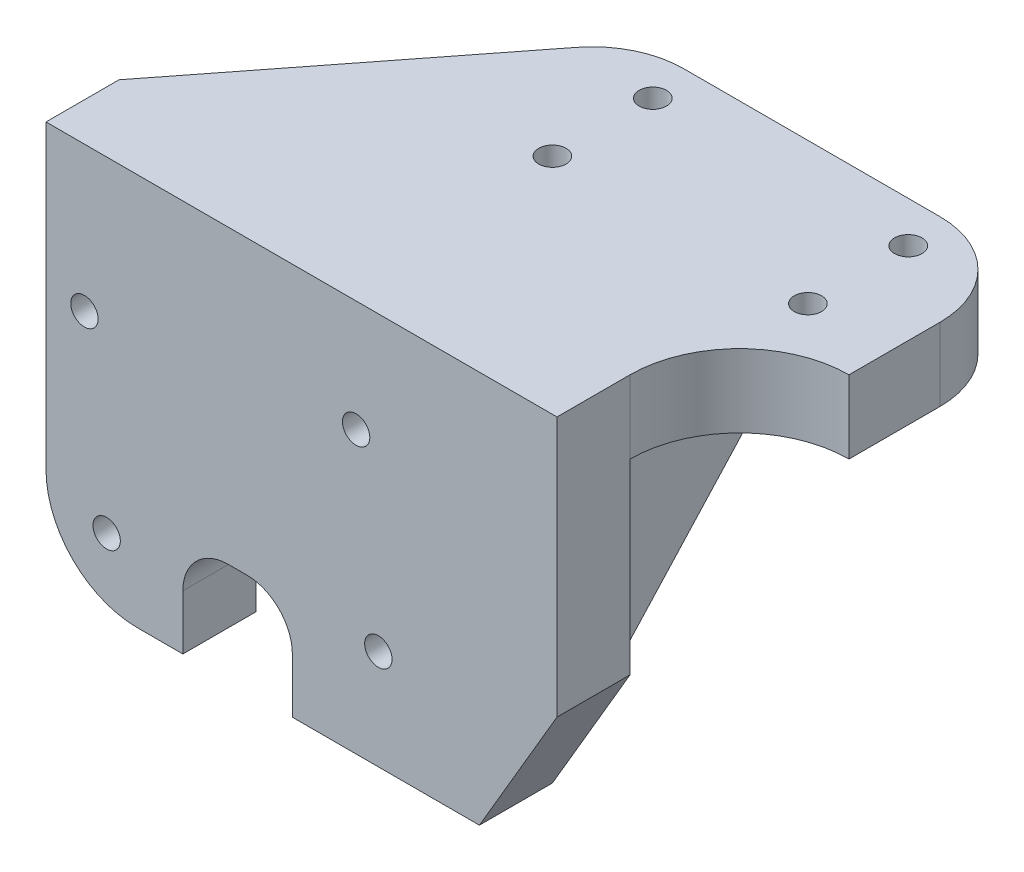
SolidWorks part; units mm, degrees
material "ABS"
ref_plane "前视基准面" through (0, 0, 0) normal (0, 0, 1) x (1, 0, 0)
ref_plane "上视基准面" through (0, 0, 0) normal (0, 1, 0) x (1, 0, 0)
ref_plane "右视基准面" through (0, 0, 0) normal (1, 0, 0) x (0, 0, -1)
sketch "草图1" plane through (0, 0, 0) normal (0, 1, 0) x (1, 0, 0)
  line L1 (-45, -20) -> (45, -20)
  line L2 (-45, -20) -> (-45, 20)
  line L3 (-45, 20) -> (45, 20)
  line L4 (45, -20) -> (45, 20)
  line L5 (-45, -20) -> (45, 20) construction
  line L6 (-45, 20) -> (45, -20) construction
  point P0 (0, 0)
  dimension "D1" = 40
  dimension "D2" = 90
extrude "凸台-拉伸1" add sketch "草图1" along normal blind 8
sketch "草图2" plane through (0, 0, 0) normal (0, -1, 0) x (1, 0, 0)
  line L0 (0, 20) -> (0, -20) construction
  line L1 (-45, 20) -> (45, 20) construction
  line L2 (45, -20) -> (-45, -20) construction
  line L4 (-14, -15.5) -> (14, -15.5) construction
  line L5 (-14, -15.5) -> (-14, -4.5) construction
  line L6 (-14, -4.5) -> (14, -4.5) construction
  line L7 (14, -15.5) -> (14, -4.5) construction
  line L8 (-14, -15.5) -> (14, -4.5) construction
  line L9 (-14, -4.5) -> (14, -15.5) construction
  circle A0 centre (-14, -4.5) radius 1.5
  circle A1 centre (-14, -15.5) radius 1.5
  circle A2 centre (14, -15.5) radius 1.5
  circle A3 centre (14, -4.5) radius 1.5
  point P6 (0, -10)
  dimension "D1" = 3
  dimension "D2" = 3
  dimension "D3" = 11
  dimension "D4" = 10
  dimension "D5" = 28
extrude "切除-拉伸1" cut sketch "草图2" against normal through all
sketch "草图3" plane through (0, 0, 0) normal (0, -1, 0) x (1, 0, 0)
  line L0 (45, 20) -> (45, -20) construction
  line L1 (-45, 20) -> (45, 20)
  line L2 (-45, 20) -> (-45, 12)
  line L3 (-45, 12) -> (45, 12)
  line L4 (45, 20) -> (45, 12)
  dimension "D1" = 8
extrude "凸台-拉伸2" add sketch "草图3" along normal blind 35
sketch "草图6" plane through (0, 0, 0) normal (0, -1, 0) x (1, 0, 0)
  line L0 (-45, 12) -> (-20, -20)
  line L1 (45, -20) -> (-45, -20) construction
  line L2 (-20, -20) -> (-45, -20)
  line L3 (-45, -20) -> (-45, 12)
  dimension "D1" = 25
extrude "切除-拉伸3" cut sketch "草图6" against normal through all
sketch "草图7" plane through (0, 8, 0) normal (0, 1, 0) x (1, 0, 0)
  line L0 (45, 20) -> (-20, 20) construction
  line L1 (23, 20) -> (45, 20)
  line L2 (23, 20) -> (23, -20)
  line L3 (23, -20) -> (45, -20)
  line L4 (45, 20) -> (45, -20)
  dimension "D1" = 22
extrude "切除-拉伸4" cut sketch "草图7" against normal through all
sketch "草图8" plane through (0, 0, 0) normal (0, -1, 0) x (1, 0, 0)
  line L0 (-45, 12) -> (23, 12) construction
  line L1 (2.5, -20) -> (-2.5, -20)
  line L2 (2.5, -20) -> (2.5, 12)
  line L3 (2.5, 12) -> (-2.5, 12)
  line L4 (-2.5, -20) -> (-2.5, 12)
  line L5 (23, -20) -> (-20, -20) construction
  line L6 (-14, -4.5) -> (14, -4.5) construction
  line L7 (0, -4.5) -> (0, -20) construction
  dimension "D1" = 5
  dimension "D2" = 2.5
extrude "凸台-拉伸3" add sketch "草图8" along normal blind 35
sketch "草图9" plane through (-2.5, 0, 0) normal (-1, 0, 0) x (0, 0, 1)
  line L0 (-20, 0) -> (12, -35)
  line L1 (12, -35) -> (-20, -35)
  line L2 (-20, -35) -> (-20, 0)
extrude "切除-拉伸5" cut sketch "草图9" against normal through all
sketch "草图14" plane through (0, 0, 20) normal (0, 0, 1) x (1, 0, 0)
  circle A0 centre (-8.5761, -24.0517) radius 1.5 construction
  circle A1 centre (-8.5761, -24.0517) radius 1.5
  circle A2 centre (-38.3525, -27.7078) radius 1.5 construction
  circle A3 centre (-38.3525, -27.7078) radius 1.5
  circle A4 centre (-40.7899, -7.8568) radius 1.5 construction
  circle A5 centre (-11.0135, -4.2008) radius 1.5 construction
  circle A6 centre (-40.7899, -7.8568) radius 1.5
  circle A7 centre (-11.0135, -4.2008) radius 1.5
extrude "切除-拉伸8" cut sketch "草图14" against normal through all
sketch "草图15" plane through (0, 0, 20) normal (0, 0, 1) x (1, 0, 0)
  line L0 (23, -35) -> (-45, -35) construction
  line L1 (-30, -35) -> (-18, -35)
  line L2 (-30, -35) -> (-30, -24)
  line L3 (-30, -24) -> (-18, -24)
  line L4 (-18, -35) -> (-18, -24)
  line L5 (-45, 8) -> (-45, -35) construction
  dimension "D1" = 12
  dimension "D2" = 15
  dimension "D3" = 11
extrude "切除-拉伸10" cut sketch "草图15" against normal through all
fillet "圆角2" radius 5 2 edges at (-30, -24, 16) (-18, -24, 16)
fillet "圆角5" radius 5 2 edges at (-2.5, 0, -4) (2.5, 0, -4)
sketch "草图16" plane through (0, 0, 12) normal (0, 0, -1) x (-1, 0, 0)
  line L0 (-23, 0) -> (-2.5, -35)
  line L1 (-2.5, -35) -> (-23, -35)
  line L2 (-23, -35) -> (-23, 0)
extrude "切除-拉伸11" cut sketch "草图16" against normal through all and the other way through all
fillet "圆角4" radius 10 3 edges at (-45, -35, 16) (-20, 4, -20) (23, 4, -20)
sketch "草图18" plane through (0, 8, 0) normal (0, 1, 0) x (1, 0, 0)
  line L0 (7.5, -12) -> (23, -12) construction
  line L2 (11, -12) -> (11, -20)
  line L3 (11, -20) -> (23, -20)
  line L4 (23, -12) -> (23, -20)
  line L5 (23, -12) -> (23, 0)
  arc A0 (23, 0) -> (11, -12) centre (23, -12) ccw
  dimension "D1" = 12
extrude "切除-拉伸12" cut sketch "草图18" against normal through all
sketch "草图19" plane through (0, 0, 12) normal (0, 0, -1) x (-1, 0, 0)
  line L0 (45, -25) -> (45, 0) construction
  line L1 (22, 0) -> (28, 0)
  line L2 (22, 0) -> (22, -20)
  line L3 (22, -20) -> (28, -20)
  line L4 (28, 0) -> (28, -20)
  line L5 (45, 0) -> (7.5, 0) construction
  dimension "D1" = 6
  dimension "D2" = 17
  dimension "D3" = 20
extrude "凸台-拉伸4" add sketch "草图19" along normal blind 20
sketch "草图20" plane through (-28, 0, 0) normal (-1, 0, 0) x (0, 0, 1)
  line L0 (-8, 0) -> (12, -20)
  line L1 (-16.1564, 0) -> (12, 0) construction
  line L2 (-8, 0) -> (12, 0) construction
  line L3 (12, -35) -> (12, -5) construction
  line L4 (12, -20) -> (-8, -20)
  line L5 (-8, -20) -> (-8, 0)
extrude "切除-拉伸13" cut sketch "草图20" against normal up to next
fillet "圆角6" radius 3 2 edges at (-22, 0, 2) (-28, 0, 2)
